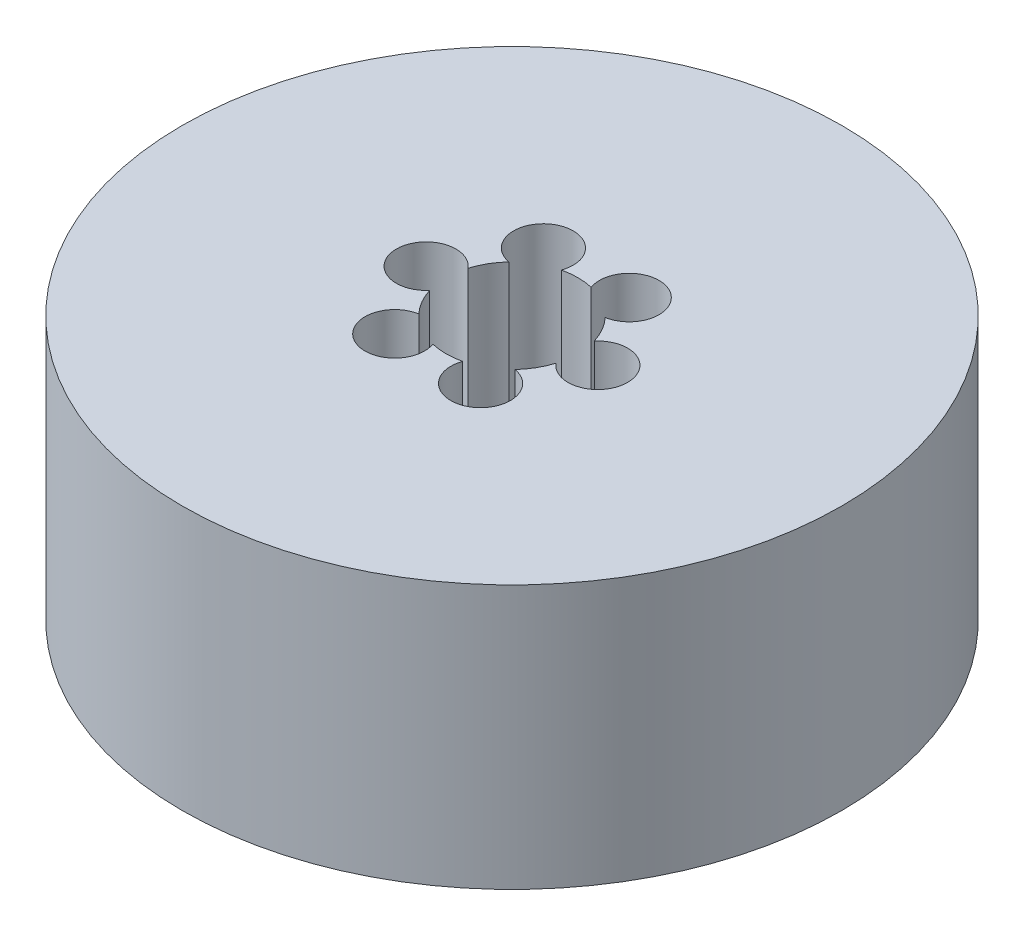
SolidWorks part; units mm, degrees
ref_plane "Front Plane" through (0, 0, 0) normal (0, 0, 1) x (1, 0, 0)
ref_plane "Top Plane" through (0, 0, 0) normal (0, 1, 0) x (1, 0, 0)
ref_plane "Right Plane" through (0, 0, 0) normal (1, 0, 0) x (0, 0, -1)
sketch "Sketch1" plane through (0, 0, 0) normal (0, 1, 0) x (1, 0, 0)
  circle A0 centre (0, 0) radius 25
  dimension "FLANGE_OD" = 50
extrude "Boss-Extrude1" add sketch "Sketch1" along normal blind 20
sketch "Sketch2" plane through (0, 0, 0) normal (0, 1, 0) x (1, 0, 0)
  circle A0 centre (0, 0) radius 5
  dimension "BORE_D" = 10
extrude "Cut-Extrude1" cut sketch "Sketch2" along normal through all
sketch "Sketch3" plane through (0, 20, 0) normal (0, 1, 0) x (1, 0, 0)
  circle A0 centre (0, 0) radius 6.5088 construction
  circle A1 centre (-6.5088, 0) radius 2.2578
  dimension "BOLT_D" = 4.5156
  dimension "BOLT_PCD" = 13.0175
extrude "Cut-Extrude2" cut sketch "Sketch3" against normal blind 14.1727
pattern_circular "CirPattern1" count 6 over 360 about axis through (0, 0, 0) along (0, 1, 0) of "Cut-Extrude2"
